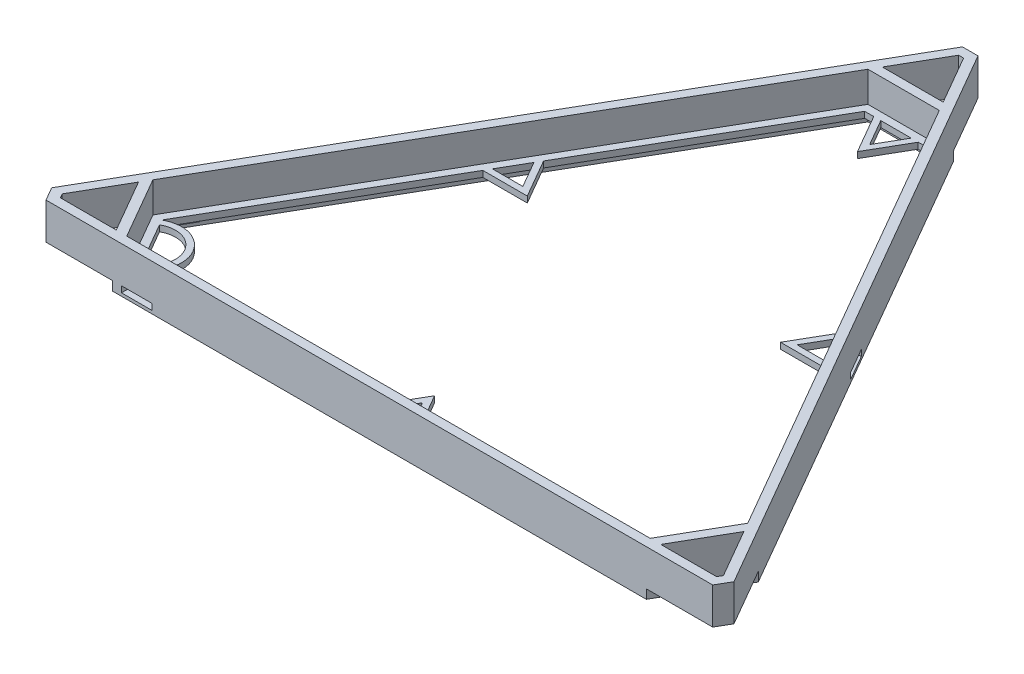
SolidWorks part; units mm, degrees
ref_plane "Front Plane" through (0, 0, 0) normal (0, 0, 1) x (1, 0, 0)
ref_plane "Top Plane" through (0, 0, 0) normal (0, 1, 0) x (1, 0, 0)
ref_plane "Right Plane" through (0, 0, 0) normal (1, 0, 0) x (0, 0, -1)
sketch "Sketch1" plane through (0, 0, 0) normal (0, 1, 0) x (1, 0, 0)
  line L17 (-4, 192.2576) -> (111, -6.9282) construction
  line L24 (4, 192.2576) -> (-111, -6.9282) construction
  line L25 (-115, 0) -> (115, 0) construction
  line L26 (0, -4.4282) -> (0, -1.4282) construction
  line L27 (-113, -3.4641) -> (-107, 0) construction
  line L28 (0, 192.2576) -> (0, 185.3294) construction
  line L29 (113, -3.4641) -> (107, 0) construction
  line L31 (-107.8246, -1.4282) -> (-108.6491, 0)
  line L39 (109.5566, -4.4282) -> (-109.5566, -4.4282)
  line L40 (-0.8246, 186.7576) -> (0.8246, 186.7576)
  line L41 (-109.5566, -4.4282) -> (-112.1132, 0)
  line L42 (-2.5566, 189.7576) -> (-112.1132, 0)
  line L43 (109.5566, -4.4282) -> (112.1132, 0)
  line L44 (-2.5566, 189.7576) -> (2.5566, 189.7576)
  line L45 (2.5566, 189.7576) -> (112.1132, 0)
  line L47 (108.6491, 0) -> (107.8246, -1.4282)
  line L50 (-99.4737, 15.8923) -> (-89.4737, -1.4282)
  line L51 (-107.8246, -1.4282) -> (-89.4737, -1.4282)
  line L52 (-99.4737, 15.8923) -> (-108.6491, 0)
  line L54 (89.4737, -1.4282) -> (107.8246, -1.4282)
  line L56 (89.4737, -1.4282) -> (99.4737, 15.8923)
  line L57 (99.4737, 15.8923) -> (108.6491, 0)
  line L58 (0, -1.4282) -> (0, 1.0718) construction
  line L59 (54.7369, 93.3788) -> (52.5718, 92.1288) construction
  line L62 (-10, 170.8653) -> (10, 170.8653)
  line L63 (-10, 170.8653) -> (-0.8246, 186.7576)
  line L64 (0.8246, 186.7576) -> (10, 170.8653)
  line L65 (94.4737, 7.2321) -> (91.8756, 8.7321) construction
  line L66 (-11.7321, 167.8653) -> (11.7321, 167.8653)
  line L67 (97.7417, 18.8923) -> (86.0096, -1.4282)
  line L68 (97.7417, 18.8923) -> (11.7321, 167.8653)
  line L69 (-54.7369, 93.3788) -> (-52.5718, 92.1288) construction
  line L71 (-94.4737, 7.2321) -> (-91.8756, 8.7321) construction
  line L72 (-97.7417, 18.8923) -> (-86.0096, -1.4282)
  line L73 (-86.0096, -1.4282) -> (86.0096, -1.4282)
  line L74 (-97.7417, 18.8923) -> (-11.7321, 167.8653)
  line L79 (91.8756, 8.7321) -> (89.7106, 9.9821) construction
  line L80 (94.8549, 18.8923) -> (84.5662, 1.0718)
  line L81 (0, 167.8653) -> (0, 165.3653) construction
  line L97 (-94.8549, 18.8923) -> (-84.5662, 1.0718) construction
  line L100 (-94.8549, 18.8923) -> (-93.8549, 17.1603) construction
  line L106 (-84.5662, 1.0718) -> (-85.5662, 2.8038) construction
  line L107 (-93.8549, 17.1603) -> (-85.5662, 2.8038)
  line L108 (50.0718, 96.4589) -> (55.0718, 87.7987)
  line L109 (41.6077, 85.7987) -> (56.2265, 85.7987)
  line L111 (50.0718, 96.4589) -> (45.0718, 87.7987)
  line L112 (45.0718, 87.7987) -> (55.0718, 87.7987)
  line L115 (56.2265, 85.7987) -> (94.8549, 18.8923)
  line L116 (48.9171, 98.4589) -> (10.2887, 165.3653)
  line L117 (41.6077, 85.7987) -> (48.9171, 98.4589)
  line L118 (-5, 165.3653) -> (5, 165.3653)
  line L121 (-55.0718, 87.7987) -> (-50.0718, 96.4589)
  line L122 (-5, 165.3653) -> (0, 156.7051)
  line L123 (5, 165.3653) -> (0, 156.7051)
  line L124 (-56.2265, 85.7987) -> (-94.8549, 18.8923)
  line L125 (0, 152.7051) -> (7.3094, 165.3653)
  line L126 (0, 152.7051) -> (-7.3094, 165.3653)
  line L127 (-10.2887, 165.3653) -> (-7.3094, 165.3653)
  line L128 (7.3094, 165.3653) -> (10.2887, 165.3653)
  line L129 (-50.0718, 96.4589) -> (-45.0718, 87.7987)
  line L130 (-55.0718, 87.7987) -> (-45.0718, 87.7987)
  line L131 (-48.9171, 98.4589) -> (-10.2887, 165.3653)
  line L132 (-41.6077, 85.7987) -> (-48.9171, 98.4589)
  line L133 (-41.6077, 85.7987) -> (-56.2265, 85.7987)
  line L134 (5, 1.0718) -> (-5, 1.0718)
  line L135 (-2.5, 5.4019) -> (-4.2321, 6.4019) construction
  line L136 (-5, 1.0718) -> (0, 9.7321)
  line L137 (0, 9.7321) -> (5, 1.0718)
  line L138 (2.5, 5.4019) -> (4.2321, 6.4019) construction
  line L139 (0, 13.7321) -> (-7.3094, 1.0718)
  line L141 (-7.3094, 1.0718) -> (-84.5662, 1.0718)
  line L143 (84.5662, 1.0718) -> (7.3094, 1.0718)
  line L144 (0, 13.7321) -> (7.3094, 1.0718)
  arc A0 (-94.8549, 18.8923) -> (-84.5662, 1.0718) centre (-89.7106, 9.9821) cw
  arc A1 (-93.8549, 17.1603) -> (-85.5662, 2.8038) centre (-89.7106, 9.9821) cw
  point P18 (0, -1.4282)
  point P41 (0, 167.8653)
  point P44 (91.8756, 8.7321)
  point P51 (-91.8756, 8.7321)
  point P55 (0, 1.0718)
  point P57 (-52.5718, 92.1288)
  point P61 (52.5718, 92.1288)
  point P65 (52.5718, 92.1288)
  point P69 (89.7106, 9.9821)
  point P74 (0, 165.3653)
  point P78 (-89.7106, 9.9821)
  point P79 (0, 165.3653)
  point P83 (-89.7106, 9.9821)
  point P89 (-52.5718, 92.1288)
  point P92 (0, 1.0718)
  point P97 (-45.8397, 93.1288)
  point P100 (-50.0718, 85.7987)
  point P106 (-4.2321, 6.4019)
  point P109 (4.2321, 6.4019)
  dimension "D1" = 8
  dimension "D2" = 8
  dimension "D3" = 8
  dimension "D4" = 230
  dimension "D5" = 230
  dimension "D6" = 230
  dimension "D7" = 3
  dimension "D8" = 3
  dimension "D9" = 3
  dimension "D10" = 2.5
  dimension "D11" = 2.5
  dimension "D12" = 2.5
  dimension "D13" = 2
  dimension "D14" = 2.5
  dimension "D15" = 2.5
  dimension "D16" = 2
  dimension "D17" = 10
  dimension "D18" = 10
  dimension "D19" = 10
  dimension "D20" = 10
  dimension "D21" = 2
  dimension "D22" = 2
extrude "Boss-Extrude1" add sketch "Sketch1" along normal blind 12 contours L45 L43 L39 L41 L42 L44 | L74 L66 L68 L67 L73 L72 | L52 L31 L51 L50 | L57 L47 L54 L56 | L64 L62 L63 L40
extrude "Boss-Extrude2" add sketch "Sketch1<4>" along normal blind 2 contours L74 L72 L73 L67 L68 L66 L80 region at (0, 0, -167.6067)
sketch "Sketch1<4>" plane through (0, 0, 0) normal (0, 1, 0) x (1, 0, 0) same geometry as "Sketch1"
sketch "Sketch2" plane through (0, 0, 0) normal (0, -1, 0) x (1, 0, 0)
  line L24 (-2.5566, -189.7576) -> (-112.1132, 0) construction
  line L25 (109.5566, 4.4282) -> (-109.5566, 4.4282) construction
  line L27 (2.5566, -189.7576) -> (112.1132, 0) construction
  line L33 (-89.4737, 1.4282) -> (-101.2058, -18.8923) construction
  line L34 (-89.4737, 1.4282) -> (-87.7417, 4.4282) construction
  line L35 (-11.7321, -167.8653) -> (11.7321, -167.8653)
  line L36 (89.4737, 1.4282) -> (87.7417, 4.4282) construction
  line L37 (99.4737, -15.8923) -> (101.2058, -18.8923) construction
  line L38 (86.0096, 1.4282) -> (97.7417, -18.8923)
  line L40 (101.2058, -18.8923) -> (87.7417, 4.4282)
  line L42 (-10, -170.8653) -> (-13.4641, -170.8653) construction
  line L43 (10, -170.8653) -> (13.4641, -170.8653) construction
  line L44 (87.7417, 4.4282) -> (-87.7417, 4.4282)
  line L45 (-97.7417, -18.8923) -> (-86.0096, 1.4282)
  line L46 (57.3349, -94.8788) -> (54.7369, -93.3788) construction
  line L47 (0, 4.4282) -> (0, 1.4282) construction
  line L48 (-87.7417, 4.4282) -> (-101.2058, -18.8923)
  line L49 (11.7321, -167.8653) -> (97.7417, -18.8923)
  line L50 (-86.0096, 1.4282) -> (86.0096, 1.4282)
  line L51 (-57.3349, -94.8788) -> (-54.7369, -93.3788) construction
  line L52 (-11.7321, -167.8653) -> (-97.7417, -18.8923)
  line L53 (-101.2058, -18.8923) -> (-13.4641, -170.8653)
  line L54 (-13.4641, -170.8653) -> (13.4641, -170.8653)
  line L55 (13.4641, -170.8653) -> (101.2058, -18.8923)
  point P66 (0, -167.8653)
  point P68 (-91.8756, -8.7321)
  point P72 (54.7369, -93.3788)
  point P75 (0, 1.4282)
  point P80 (-54.7369, -93.3788)
  dimension "D4" = 3
  dimension "D5" = 3
  dimension "D6" = 3
extrude "Boss-Extrude3" add sketch "Sketch2" along normal blind 3
sketch "Sketch4" plane through (0, 0, 4.4282) normal (0, 0, 1) x (1, 0, 0)
  line L1 (-84.7417, 0) -> (-84.7417, -2)
  line L2 (-97.7417, 0) -> (-11.7321, 0) construction
  line L3 (-84.7417, -2) -> (-74.7417, -2)
  line L4 (-74.7417, -2) -> (-74.7417, 0)
  line L5 (-74.7417, 0) -> (-84.7417, 0)
  line L6 (-2.5566, 0) -> (-112.1132, 0) construction
  line L7 (-87.7417, 0) -> (-84.7417, 0) construction
  dimension "D1" = 3
  dimension "D2" = 2
  dimension "D3" = 10
extrude "Cut-Extrude1" cut sketch "Sketch4" against normal blind 6
sketch "Sketch5" plane through (-84.0849, 0, -48.5465) normal (-0.866, 0, -0.5) x (-0.5, 0, 0.866)
  line L0 (34.2417, 0) -> (31.2417, 0) construction
  line L1 (-50.9434, 0) -> (58.6132, 0) construction
  line L2 (31.2417, 0) -> (31.2417, -2)
  line L3 (31.2417, -2) -> (21.2417, -2)
  line L4 (21.2417, -2) -> (21.2417, 0)
  line L5 (21.2417, 0) -> (31.2417, 0)
  dimension "D1" = 3
  dimension "D2" = 2
  dimension "D3" = 10
extrude "Cut-Extrude2" cut sketch "Sketch5" against normal blind 6
sketch "Sketch6" plane through (84.0849, 0, -48.5465) normal (0.866, 0, -0.5) x (-0.5, 0, -0.866)
  line L0 (-34.2417, 0) -> (141.2417, 0) construction
  line L1 (58.5, 0) -> (48.5, 0)
  line L2 (48.5, 0) -> (48.5, -2)
  line L3 (48.5, -2) -> (58.5, -2)
  line L4 (58.5, -2) -> (58.5, 0)
  point P8 (53.5, 0)
  dimension "D1" = 10
  dimension "D2" = 2
extrude "Cut-Extrude3" cut sketch "Sketch6" against normal blind 6
